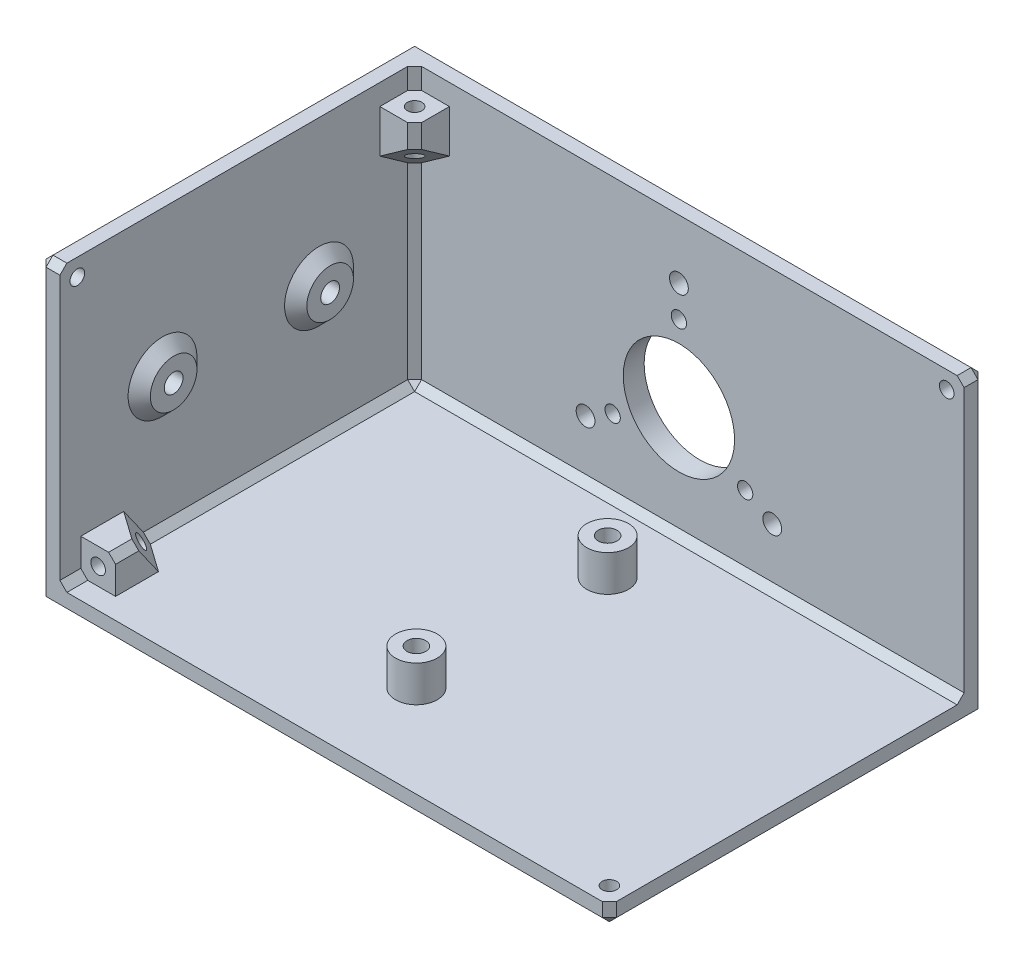
SolidWorks part; units mm, degrees
ref_plane "前视基准面" through (0, 0, 0) normal (0, 0, 1) x (1, 0, 0)
ref_plane "上视基准面" through (0, 0, 0) normal (0, 1, 0) x (1, 0, 0)
ref_plane "右视基准面" through (0, 0, 0) normal (1, 0, 0) x (0, 0, -1)
other "Configuration Table"
sketch "草图2" plane through (0, 0, 0) normal (0, 1, 0) x (1, 0, 0)
  line L0 (0, 36.6922) -> (0, -33.4547) construction
  line L1 (-41, -27) -> (41, -27)
  line L2 (-41, -27) -> (-41, 27)
  line L3 (-41, 27) -> (41, 27)
  line L4 (41, -27) -> (41, 27)
  line L5 (-41, -27) -> (41, 27) construction
  line L6 (-41, 27) -> (41, -27) construction
  line L7 (0, 0) -> (17.1605, 0) construction
  circle A0 centre (0, 13.75) radius 1.35
  circle A1 centre (0, -13.75) radius 1.35
  circle A2 centre (38.5, -24.5) radius 1.05
  point P0 (0, 0)
  dimension "D1" = 27.5
  dimension "D2" = 2.7
  dimension "D5" = 2.1
  dimension "D6" = 2.5
  dimension "D7" = 2.5
  dimension "D3" = 54
  dimension "D4" = 82
extrude "凸台-拉伸1" add sketch "草图2" along normal blind 3
sketch "草图3" plane through (0, 3, 0) normal (0, 1, 0) x (1, 0, 0)
  circle A0 centre (0, 13.75) radius 3
  circle A1 centre (0, -13.75) radius 3
  circle A2 centre (0, -13.75) radius 1.35 construction
  circle A3 centre (0, 13.75) radius 1.35 construction
  circle A4 centre (0, -13.75) radius 1.35
  circle A5 centre (0, 13.75) radius 1.35
  dimension "D1" = 6
extrude "凸台-拉伸2" add sketch "草图3" along normal blind 5.2
sketch "草图4" plane through (0, 3, 0) normal (0, 1, 0) x (1, 0, 0)
  line L0 (41, -27) -> (41, 27) construction
  line L1 (-41, 27) -> (41, 27)
  line L2 (-41, 27) -> (-41, 24)
  line L3 (-41, 24) -> (41, 24)
  line L4 (41, 27) -> (41, 24)
  dimension "D1" = 3
extrude "凸台-拉伸3" add sketch "草图4" along normal blind 40
sketch "草图5" plane through (0, 0, -27) normal (0, 0, -1) x (-1, 0, 0)
  line L0 (0, 56.892) -> (0, -75.3135) construction
  line L1 (119.0968, 19) -> (-52.3222, 19) construction
  line L2 (-41, 0) -> (41, 0) construction
  circle A0 centre (-13.4234, 11.25) radius 1.35
  circle A1 centre (-9.5263, 13.5) radius 1.1
  circle A2 centre (13.4234, 11.25) radius 1.35
  circle A3 centre (9.5263, 13.5) radius 1.1
  circle A4 centre (0, 30) radius 1.1
  circle A5 centre (0, 34.5) radius 1.35
  circle A18 centre (0, 19) radius 8
  point P1 (0, 19)
  dimension "D2" = 16
  dimension "D1" = 19
extrude "切除-拉伸1" cut sketch "草图5" against normal blind 4
sketch "草图6" plane through (-41, 0, 0) normal (-1, 0, 0) x (0, 0, 1)
  line L0 (1, 61.505) -> (1, -12.795) construction
  line L1 (-27, 43) -> (27, 43)
  line L2 (-27, 43) -> (-27, 0)
  line L3 (-27, 0) -> (27, 0)
  line L4 (27, 43) -> (27, 0)
  line L5 (-33.8356, 22) -> (37.2417, 22) construction
  circle A1 centre (-10.25, 22) radius 1.35
  circle A2 centre (12.25, 22) radius 1.35
  circle A3 centre (24.5, 40.5) radius 1.05
  point P8 (-27, 21.5)
  dimension "D3" = 22.5
  dimension "D4" = 2.7
  dimension "D5" = 2.5
  dimension "D6" = 2.5
  dimension "D7" = 2.1
  dimension "D1" = 28
  dimension "D2" = 21
extrude "凸台-拉伸4" add sketch "草图6" against normal blind 3
sketch "草图7" plane through (-38, 0, 0) normal (1, 0, 0) x (0, 0, -1)
  circle A0 centre (-12.25, 22) radius 3.35
  circle A1 centre (-12.25, 22) radius 1.35 construction
  circle A2 centre (10.25, 22) radius 1.35 construction
  circle A3 centre (10.25, 22) radius 1.35
  circle A4 centre (-12.25, 22) radius 1.35
  circle A5 centre (10.25, 22) radius 3.35
  dimension "D1" = 2
extrude "凸台-拉伸5" add sketch "草图7" along normal blind 1.6
ref_plane "基准面1" through (0, 40, 0) normal (0, 1, 0) x (1, 0, 0)
sketch "草图8" plane through (0, 40, 0) normal (0, 1, 0) x (1, 0, 0)
  line L0 (-38, 24) -> (41, 24) construction
  line L1 (-41, 27) -> (-33, 27)
  line L2 (-41, 27) -> (-41, 19)
  line L3 (-41, 19) -> (-33, 19)
  line L4 (-33, 27) -> (-33, 19)
  line L5 (-38, -27) -> (-38, 24) construction
  circle A0 centre (-35.5, 21.5) radius 1.05
  dimension "D1" = 2.1
  dimension "D2" = 2.5
  dimension "D3" = 2.5
  dimension "D4" = 8
  dimension "D5" = 8
extrude "凸台-拉伸6" add sketch "草图8" against normal blind 3
ref_plane "基准面2" through (0, 0, 24) normal (0, 0, 1) x (1, 0, 0)
sketch "草图9" plane through (0, 0, 24) normal (0, 0, 1) x (1, 0, 0)
  line L0 (-41, 0) -> (-41, 8)
  line L1 (-41, 0) -> (-33, 0)
  line L2 (-33, 0) -> (-33, 8)
  line L3 (-41, 8) -> (-33, 8)
  line L4 (-41, 0) -> (41, 0) construction
  line L5 (-41, 43) -> (-41, 0) construction
  circle A0 centre (-35.5, 5.5) radius 1.05
  point P6 (0, 0)
  dimension "D1" = 2.1
  dimension "D2" = 8
  dimension "D3" = 8
extrude "凸台-拉伸7" add sketch "草图9" against normal blind 3
sketch "草图11" plane through (0, 0, -27) normal (0, 0, -1) x (-1, 0, 0)
  line L0 (-41, 43) -> (41, 43) construction
  line L1 (-41, 43) -> (-41, 0) construction
  circle A0 centre (-38.5, 40.5) radius 1.05
  dimension "D1" = 2.1
  dimension "D3" = 2.5
  dimension "D2" = 2.5
extrude "切除-拉伸2" cut sketch "草图11" against normal blind 5
chamfer "倒角1" distance 1 angle 45 19 edges at (41, 1.5, 27) (-33, 8, 22.5) (-38, 3, 25.5) (-39.5, 43, 27) (-33, 38.5, -19) (-41, 0, 0) (-41, 21.5, -27) (-38, 3, -1.5) (-38, 20, -24) (-38, 41.5, -24) (0, 0, -27) (1.5, 3, -24) (-41, 43, 0) (0, 43, -27) (41, 0, 0) (41, 21.5, -27) (0, 0, 27) (-41, 21.5, 27) (41, 43, -25.5)
chamfer "倒角2" distance 6 angle 45 2 edges at (-37.5, 37, -23.5) (-37.5, 3.5, 21)
chamfer "倒角3" distance 1.6 angle 45 2 edges at (-38, 22, -6.9) (-38, 22, 15.6)
